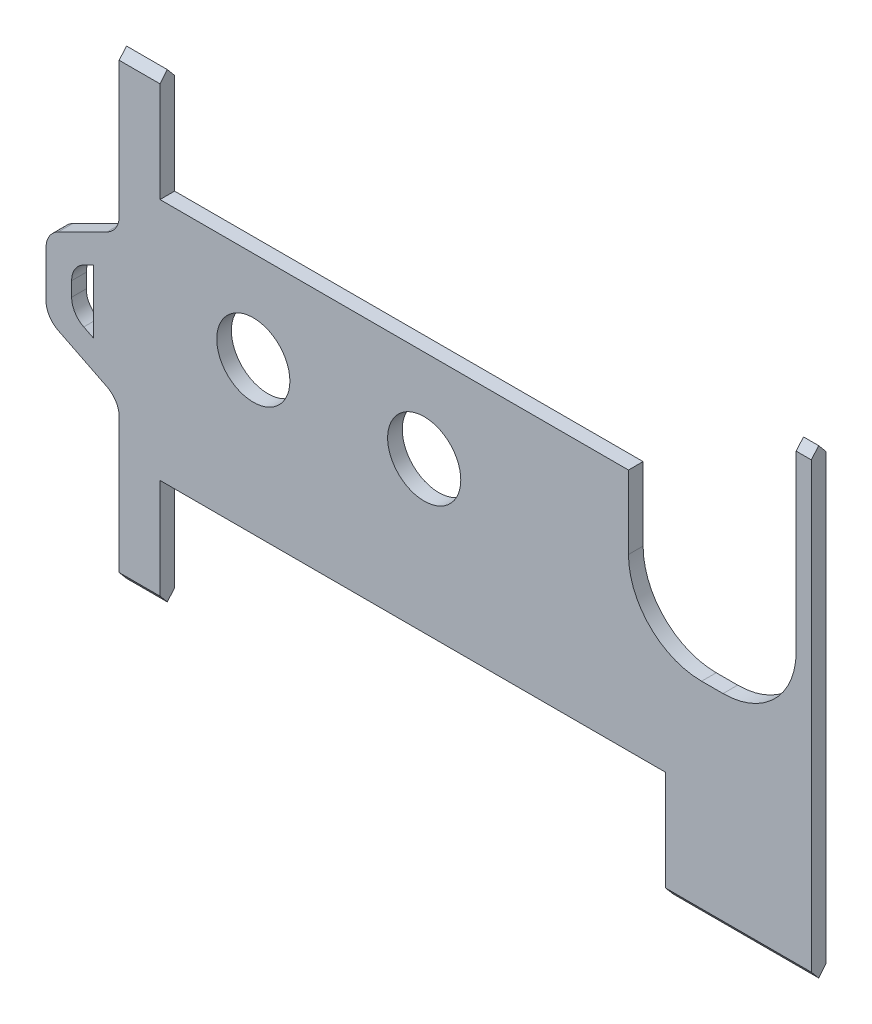
SolidWorks part; units mm, degrees
ref_plane "Front Plane" through (0, 0, 0) normal (0, 0, 1) x (1, 0, 0)
ref_plane "Top Plane" through (0, 0, 0) normal (0, 1, 0) x (1, 0, 0)
ref_plane "Right Plane" through (0, 0, 0) normal (1, 0, 0) x (0, 0, -1)
sketch "Sketch1" plane through (0, 0, 11.1483) normal (0, 0, 1) x (1, 0, 0)
  line L0 (22.423, 106.8975) -> (12.423, 101.8975)
  line L5 (22.223, 125.272) -> (22.223, 68.523) construction
  line L10 (12.423, 101.8975) -> (12.423, 91.8975)
  line L11 (117.248, 128.723) -> (22.223, 128.723) construction
  line L12 (117.248, 128.723) -> (117.248, 65.072) construction
  line L13 (117.248, 65.072) -> (22.223, 65.072) construction
  line L14 (22.223, 128.723) -> (22.223, 65.072) construction
  line L15 (117.048, 128.523) -> (22.423, 128.523)
  line L16 (22.423, 128.523) -> (22.423, 65.272)
  line L17 (117.048, 65.272) -> (22.423, 65.272)
  line L18 (117.048, 128.523) -> (117.048, 65.272)
  line L19 (12.423, 91.8975) -> (22.423, 86.8975)
  line L20 (92.048, 128.523) -> (92.048, 93.523)
  line L21 (92.048, 93.523) -> (117.048, 93.523)
  line L22 (114.9757, 128.523) -> (114.9757, 93.523)
  line L25 (22.423, 106.8975) -> (22.423, 86.8975)
  line L26 (15.923, 94.0606) -> (18.923, 92.5606)
  line L27 (18.923, 101.2344) -> (18.923, 92.5606)
  line L28 (18.923, 101.2344) -> (15.923, 99.7344)
  line L29 (15.923, 99.7344) -> (15.923, 94.0606)
  line L30 (-882.952, 96.8975) -> (49117.048, 96.8975) construction
  line L31 (28.005, 130.223) -> (28.005, 127.223) construction
  line L32 (28.005, 128.523) -> (97.123, 128.523)
  line L33 (28.005, 128.523) -> (28.005, 113.523)
  line L34 (28.005, 113.523) -> (97.123, 113.523)
  line L35 (97.123, 128.523) -> (97.123, 113.523)
  line L37 (97.123, 130.223) -> (97.123, 127.223) construction
  line L38 (28.005, 80.272) -> (97.123, 80.272)
  line L39 (97.123, 65.272) -> (97.123, 80.272)
  line L40 (28.005, 65.272) -> (97.123, 65.272)
  line L41 (28.005, 65.272) -> (28.005, 80.272)
  circle A0 centre (40.759, 100.906) radius 5
  circle A1 centre (64.123, 100.881) radius 5
  point P4 (22.423, 96.8975)
  point P8 (12.423, 96.8975)
  point P34 (117.048, 96.8975)
  dimension "D7" = 10
  dimension "D8" = 10
  dimension "D1" = 0.2
  dimension "D2" = 10
  dimension "D3" = 10
  dimension "D4" = 20
  dimension "D5" = 35
  dimension "D6" = 25
  dimension "D9" = 3.5
  dimension "D10" = 15
  dimension "D11" = 6.5
extrude "Boss-Extrude1" add sketch "Sketch1" along normal mid plane 2 contours L18 L15 L16 L17 | L10 L19 L16 L0 | L15 L22 L21 L18 region at (22.1994, 96.8975, 11.1483) region at (66.0198, 93.1247, 11.1483) region at (116.0118, 111.023, 11.1483)
sketch "Sketch2" plane through (22.423, 0, 0) normal (-1, 0, 0) x (0, 0, 1)
  line L5 (-986.1517, 96.8975) -> (49013.8483, 96.8975) construction
  line L6 (13.8483, 68.523) -> (13.8483, 125.272) construction
  line L7 (10.1013, 128.523) -> (10.1013, 127.1682)
  line L8 (12.1953, 127.1682) -> (11.1483, 128.4124)
  line L10 (12.1953, 66.6268) -> (12.1953, 65.272)
  line L11 (12.1953, 65.272) -> (10.1013, 65.272)
  line L12 (11.1483, 65.3826) -> (10.1013, 66.6268)
  line L13 (12.1953, 66.6268) -> (11.1483, 65.3826)
  line L14 (11.1483, 65.3826) -> (10.1013, 66.6268)
  line L15 (12.1953, 66.6268) -> (11.1483, 65.3826)
  line L16 (10.1013, 65.272) -> (10.1013, 66.6268)
  line L17 (12.1483, 65.272) -> (10.1483, 65.272) construction
  line L18 (11.1483, 128.4124) -> (10.1013, 127.1682)
  line L19 (12.1953, 128.523) -> (10.1013, 128.523)
  line L20 (12.1953, 127.1682) -> (12.1953, 128.523)
  point P9 (13.8483, 96.8975)
  dimension "D2" = 0.2
extrude "Cut-Extrude1" cut sketch "Sketch2" against normal through all
fillet "Fillet1" radius 10 2 edges at (92.048, 93.523, 11.1483) (114.9757, 93.523, 11.1483)
fillet "Fillet2" radius 3 6 edges at (15.923, 99.7344, 11.1483) (15.923, 94.0606, 11.1483) (22.423, 106.8975, 11.1483) (12.423, 101.8975, 11.1483) (12.423, 91.8975, 11.1483) (22.423, 86.8975, 11.1483)
